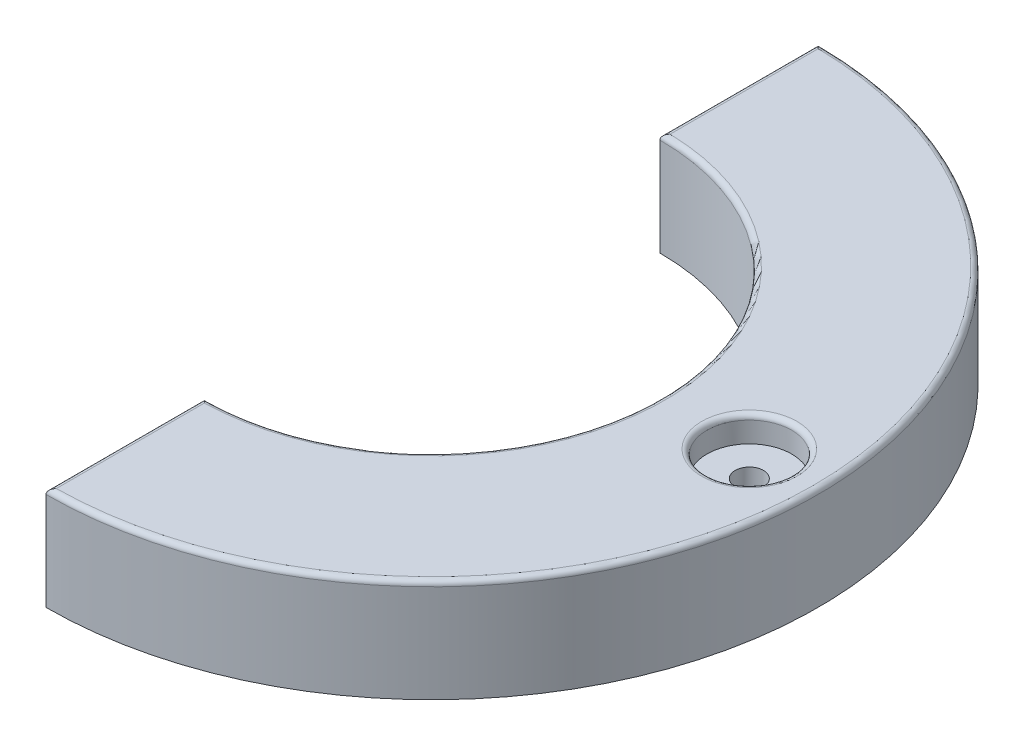
SolidWorks part; units mm, degrees
material "ABS"
ref_plane "Front Plane" through (0, 0, 0) normal (0, 0, 1) x (1, 0, 0)
ref_plane "Top Plane" through (0, 0, 0) normal (0, 1, 0) x (1, 0, 0)
ref_plane "Right Plane" through (0, 0, 0) normal (1, 0, 0) x (0, 0, -1)
sketch "Sketch1" plane through (0, 0, 0) normal (0, 1, 0) x (1, 0, 0)
  line L0 (0, 0) -> (0, 75) construction
  line L1 (0, 0) -> (0, -75) construction
  line L2 (0, 44.25) -> (0, 75)
  line L3 (0, -75) -> (0, -44.25)
  line L6 (50, -75) -> (50, 75) construction
  arc A0 (0, 75) -> (0, -75) centre (0, 0) cw
  arc A1 (0, 44.25) -> (0, -44.25) centre (0, 0) cw
  circle A2 centre (0, 0) radius 44.25 construction
  point P0 (0, 0)
  dimension "D3" = 88.5
  dimension "D1" = 75
  dimension "D2" = 75
  dimension "D4" = 50
extrude "Boss-Extrude1" add sketch "Sketch1" along normal blind 20
sketch "Sketch3" plane through (0, 0, 0) normal (-1, 0, 0) x (0, 0, 1)
  line L1 (-75, 0) -> (-44.25, 0) construction
  line L2 (-75, 20) -> (-75, 0) construction
  line L3 (44.25, 0) -> (75, 0) construction
  line L4 (75, 20) -> (75, 0) construction
  circle A0 centre (-63, 10) radius 2.1
  circle A1 centre (63, 10) radius 2.1
  point P4 (-59.625, 0)
  point P9 (59.625, 0)
  point P12 (75, 10)
  dimension "D3" = 4.2
  dimension "D6" = 4.2
  dimension "D1" = 10
  dimension "D2" = 12
  dimension "D4" = 10
  dimension "D5" = 12
extrude "Cut-Extrude2" cut sketch "Sketch3" against normal blind 30
sketch "Sketch4" plane through (0, 20, 0) normal (0, 1, 0) x (1, 0, 0)
  arc A0 (0, -44.25) -> (0, 44.25) centre (0, 0) ccw construction
  circle A1 centre (61.63, 0) radius 8.25
  point P0 (61.63, 0)
  point P1 (44.25, 0)
  dimension "D2" = 16.5
  dimension "D1" = 17.38
extrude "Cut-Extrude3" cut sketch "Sketch4" against normal blind 5
fillet "Fillet1" radius 1 1 edges at (61.63, 20, 8.25)
fillet "Fillet2" radius 1 1 edges at (44.25, 20, 0)
fillet "Fillet3" radius 1 3 edges at (0, 20, -60.125) (0, 20, 60.125) (75, 20, 0)
sketch "Sketch5" plane through (0, 15, 0) normal (0, 1, 0) x (1, 0, 0)
  line L0 (53.38, 0) -> (69.88, 0) construction
  line L1 (61.63, 8.25) -> (61.63, -8.25) construction
  circle A0 centre (61.63, 0) radius 8.25 construction
  circle A1 centre (61.63, 0) radius 8.25 construction
  circle A2 centre (61.63, 0) radius 2.75
  dimension "D1" = 5.5
extrude "Cut-Extrude4" cut sketch "Sketch5" against normal blind 20
sketch "Sketch6" plane through (0, 0, 0) normal (0, -1, 0) x (1, 0, 0)
  line L0 (58.88, 0) -> (64.38, 0) construction
  line L1 (61.63, 2.75) -> (61.63, -2.75) construction
  circle A0 centre (61.63, 0) radius 2.75 construction
  circle A1 centre (61.63, 0) radius 5
  dimension "D1" = 10
extrude "Cut-Extrude5" cut sketch "Sketch6" against normal blind 4
